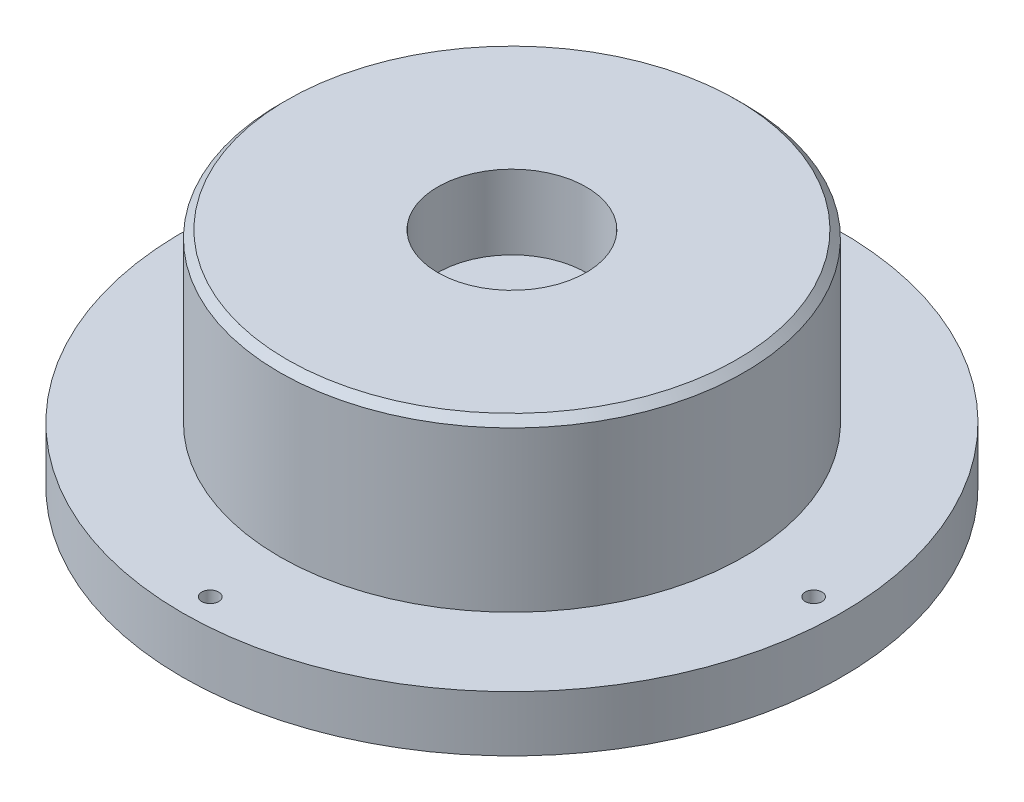
SolidWorks part; units mm, degrees
ref_plane "Front Plane" through (0, 0, 0) normal (0, 0, 1) x (1, 0, 0)
ref_plane "Top Plane" through (0, 0, 0) normal (0, 1, 0) x (1, 0, 0)
ref_plane "Right Plane" through (0, 0, 0) normal (1, 0, 0) x (0, 0, -1)
sketch "Sketch1" plane through (0, 0, 0) normal (0, 1, 0) x (1, 0, 0)
  circle A0 centre (0, 0) radius 39.75
  dimension "D1" = 79.5
extrude "Boss-Extrude1" add sketch "Sketch1" along normal blind 28.575
sketch "Sketch2" plane through (0, 28.575, 0) normal (0, 1, 0) x (1, 0, 0)
  circle A0 centre (0, 0) radius 12.7
  dimension "D1" = 25.4
sketch "Sketch3" plane through (0, 0, 0) normal (0, -1, 0) x (1, 0, 0)
  circle A0 centre (0, 0) radius 56.388
  dimension "D1" = 112.776
extrude "Boss-Extrude3" add sketch "Sketch3" along normal blind 9.525
chamfer "Chamfer1" distance 1.27 angle 45 1 edges at (0, 28.575, 39.75)
hole_wizard "Tap Drill for #4-40 Tap1" positions "Sketch9" profile "Sketch10" hole size "#4-40" standard "ANSI Inch" end condition through all
sketch "Sketch9" plane through (0, 0, 0) normal (0, 1, 0) x (1, 0, 0)
  circle A0 centre (0, 0) radius 51.6255 construction
  point P0 (0, 51.6255)
  point P2 (51.6255, 0)
  point P4 (0, -51.6255)
  point P6 (-51.6255, 0)
  dimension "D1" = 103.251
sketch "Sketch10" plane through (0, 0, -51.6255) normal (1, 0, 0) x (0, 0, 1)
  line L0 (0, 0) -> (0, 9.525)
  line L1 (0, 9.525) -> (1.4351, 9.525)
  line L2 (1.4351, 9.525) -> (1.4351, 0)
  line L5 (1.4351, 0) -> (0, 0)
  line L11 (0, -6.35) -> (0, 107.95) construction
  dimension "Thru Hole Dia." = 2.8702
  dimension "Thru Hole Depth" = 9.525
extrude "Cut-Extrude1" cut sketch "Sketch2" against normal blind 12.7
